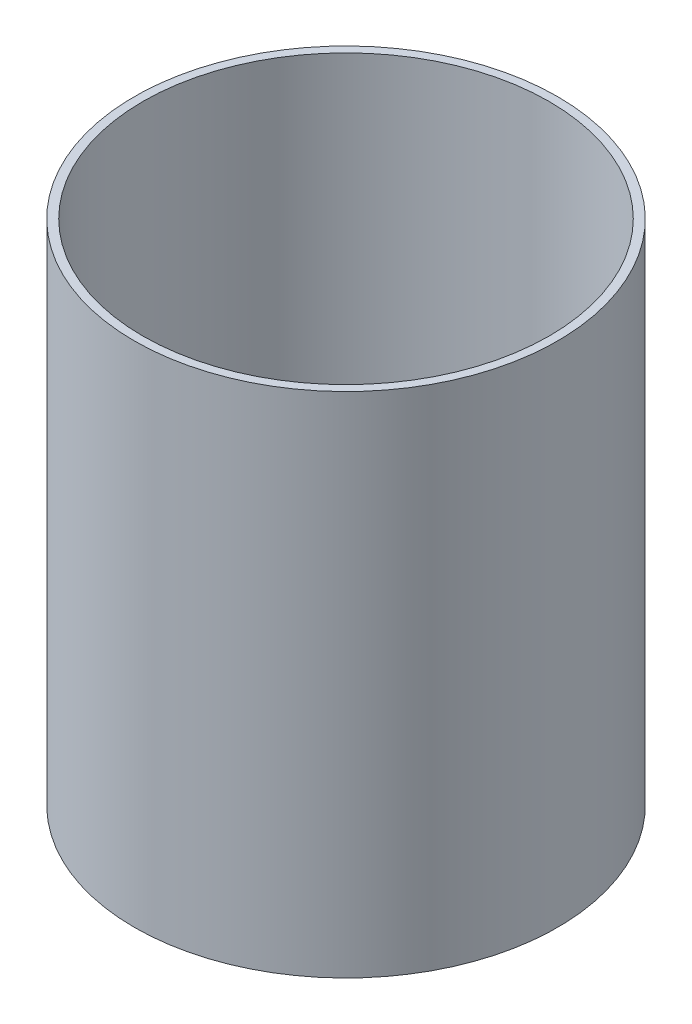
SolidWorks part; units mm, degrees
material "7075-T6 (SN)"
ref_plane "Front Plane" through (0, 0, 0) normal (0, 0, 1) x (1, 0, 0)
ref_plane "Top Plane" through (0, 0, 0) normal (0, 1, 0) x (1, 0, 0)
ref_plane "Right Plane" through (0, 0, 0) normal (1, 0, 0) x (0, 0, -1)
sketch "Sketch1" plane through (0, 0, 0) normal (0, 1, 0) x (1, 0, 0)
  circle A0 centre (0, 0) radius 1250
  circle A1 centre (0, 0) radius 1200
  circle A2 centre (0, 0) radius 1225 construction
  dimension "D1" = 2500
  dimension "D2" = 2450
  dimension "D3" = 2400
extrude "Boss-Extrude1" add sketch "Sketch1" along normal blind 3000
